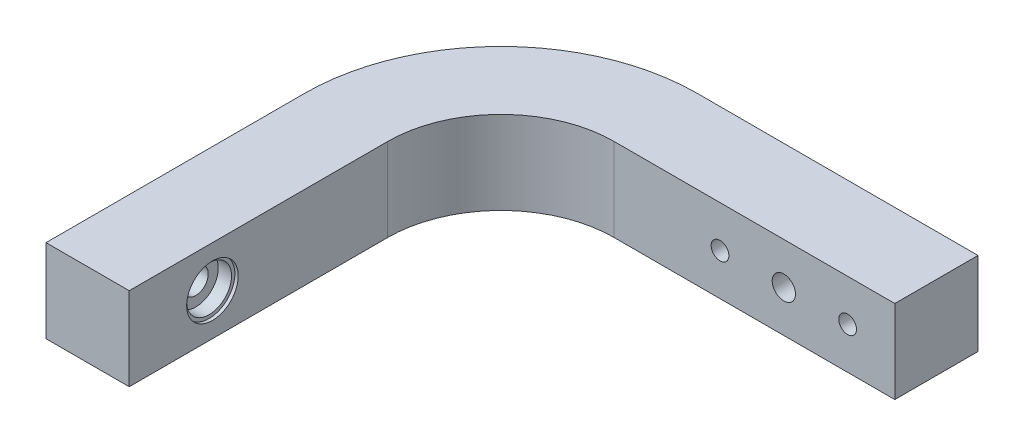
SolidWorks part; units mm, degrees
ref_plane "Front Plane" through (0, 0, 0) normal (0, 0, 1) x (1, 0, 0)
ref_plane "Top Plane" through (0, 0, 0) normal (0, 1, 0) x (1, 0, 0)
ref_plane "Right Plane" through (0, 0, 0) normal (1, 0, 0) x (0, 0, -1)
ref_axis "Z" through (0, 0, -59.2654) along (0, 0, 1)
sketch "Sketch1" plane through (0, 0, 0) normal (0, 1, 0) x (1, 0, 0)
  line L0 (-30.6, 0) -> (30.6, 0) construction
  line L1 (-66, -35.4) -> (-66, -82)
  line L2 (-66, -82) -> (-51, -82)
  line L3 (-51, -82) -> (-51, -35.4)
  line L4 (-30.6, -15) -> (30.6, -15) construction
  line L5 (0, -15) -> (0, 0) construction
  line L6 (51, -82) -> (51, -35.4) construction
  line L7 (66, -82) -> (51, -82) construction
  line L8 (66, -35.4) -> (66, -82) construction
  line L9 (30.6, 0) -> (30.6, -15) construction
  line L10 (20, -15) -> (20, 0)
  line L11 (-30.6, -15) -> (20, -15)
  line L12 (-30.6, 0) -> (20, 0)
  line L13 (0, 59.2654) -> (0, -30.9346) construction
  arc A0 (-30.6, 0) -> (-66, -35.4) centre (-30.6, -35.4) ccw
  arc A1 (-51, -35.4) -> (-30.6, -15) centre (-30.6, -35.4) cw
  arc A2 (51, -35.4) -> (30.6, -15) centre (30.6, -35.4) ccw construction
  arc A3 (30.6, 0) -> (66, -35.4) centre (30.6, -35.4) cw construction
  dimension "D3" = 20.4
  dimension "D1" = 102
  dimension "D2" = 15
  dimension "D4" = 67
  dimension "D5" = 20
extrude "Boss-Extrude1" add sketch "Sketch1" along normal blind 7.5 and the other way blind 7.5
sketch "Sketch2" plane through (-51, 0, 0) normal (-1, 0, 0) x (0, 0, 1)
  line L1 (45.1, 0) -> (-45.1, 0) construction
  line L2 (0, -8.25) -> (0, 8.25) construction
  circle A0 centre (67, 0) radius 2.25
  dimension "D1" = 4.5
  dimension "D2" = 67
extrude "Cut-Extrude1" cut sketch "Sketch2" against normal through all both and the other way through all
ref_axis "Axis2" through (-85.609, 0, 67) along (1, 0, 0)
sketch "Sketch3" plane through (0, 0, 0) normal (0, 0, -1) x (-1, 0, 0)
  line L0 (-11.5, 0) -> (11.5, 0) construction
  circle A0 centre (0, 0) radius 2.1
  circle A1 centre (-11.5, 0) radius 1.6
  circle A2 centre (11.5, 0) radius 1.6
  dimension "D1" = 4.2
  dimension "D3" = 3.2
  dimension "D2" = 23
extrude "Cut-Extrude2" cut sketch "Sketch3" against normal through all
sketch "Sketch5" plane through (0, 0, 0) normal (0, 1, 0) x (1, 0, 0)
  line L0 (-66, -71.65) -> (-65.4, -71.65)
  line L1 (-65.4, -71.65) -> (-65.4, -71.05)
  line L2 (-65.4, -71.05) -> (-63, -71.05)
  line L3 (-63, -71.05) -> (-63, -67)
  line L4 (-66, -71.65) -> (-66, -67)
  line L5 (-92.6767, -67) -> (-43.9581, -67) construction
  line L6 (-84.5878, -67) -> (-79.7197, -67) construction
  line L7 (-66, -67) -> (-63, -67)
  line L9 (-66, -35.4) -> (-66, -82) construction
  line L10 (-58.5, -78.0435) -> (-58.5, -69.815) construction
  line L11 (-66, -82) -> (-51, -82) construction
  line L12 (-51, -67) -> (-54, -67)
  line L13 (-51, -71.65) -> (-51, -67)
  line L14 (-54, -71.05) -> (-54, -67)
  line L15 (-51.6, -71.05) -> (-54, -71.05)
  line L16 (-51.6, -71.65) -> (-51.6, -71.05)
  line L17 (-51, -71.65) -> (-51.6, -71.65)
  point P14 (-58.5, -82)
  dimension "D1" = 0.6
  dimension "D2" = 4.65
  dimension "D3" = 8.1
  dimension "D4" = 3
revolve "bearing-seats" cut sketch "Sketch5" angle 360 about L6
equation "\"width\"= \"EyeDiameter\" + \"EyeClearance\""
equation "\"prongwidth\"= \"L2Thickness\""
equation "\"D2@Sketch1\"=\"prongwidth\""
equation "\"D3@Sketch1\"=\"width\"/5"
equation "\"pronglength\"= \"BasePlaneDistance\"'model implicitly adds clearance (of prongwidth) to the hole drilled at the baseplanedistance"
equation "\"D4@Sketch1\"=\"pronglength\""
equation "\"D1@Boss-Extrude1\"=\"prongwidth\"/2"
equation "\"D2@Boss-Extrude1\"=\"prongwidth\"/2"
equation "\"lbracket-plane-to-axis\"= \"BasePlaneDistance\""
equation "\"D2@Sketch2\"=\"lbracket-plane-to-axis\""
equation "\"EyeDiameter\" = 100"
equation "\"BasePlaneDistance\" = \"EyeDiameter\"/2+\"L2Thickness\"+\"EyeClearance\""
equation "\"EyeClearance\" = 2"
equation "\"D1@Sketch1\"=\"EyeDiameter\"+\"EyeClearance\""
equation "\"BearingDepth\"= 6"
equation "\"BearingHousingID\"=4.5"
equation "\"BearingFlangeThickness\"= 0.75"
equation "\"BearingFlangeOD\"=7.5"
equation "\"PrinterFilamentThickness\"= 0.1"
equation "\"ApplyPrinterOffset\"= 1'if 1, adjust hole sizes to try and make pressfits work with the 3d printer"
equation "\"L2Thickness\" = 15"
equation "\"L2_ID\" = 20"
equation "\"vx\" = 0"
equation "\"vy\" = 0"
equation "\"vz\" = 100"
equation "\"parametric_end\" = 1"
equation "\"Rw_3_xx\" = -(\"vz\")/sqr((\"vx\")^2 + (\"vz\")^2)"
equation "\"Rw_3_xy\" = 0"
equation "\"Rw_3_xz\" = (\"vx\")/sqr((\"vx\")^2 + (\"vz\")^2)"
equation "\"Rw_3_zx\" = (\"vx\")/sqr((\"vx\")^2 + (\"vy\")^2 + (\"vz\")^2)"
equation "\"Rw_3_zy\" = (\"vy\")/sqr((\"vx\")^2 + (\"vy\")^2 + (\"vz\")^2)"
equation "\"Rw_3_zz\" = (\"vz\")/sqr((\"vx\")^2 + (\"vy\")^2 + (\"vz\")^2)"
equation "\"Rw_3_yx\" = (\"vx\")*(\"vy\")/sqr((\"vx\")^4 + (\"vx\")^2*(\"vy\")^2 + 2*(\"vx\")^2*(\"vz\")^2 + (\"vy\")^2*(\"vz\")^2 + (\"vz\")^4)"
equation "\"Rw_3_yy\" = -sqr((\"vx\")^2 + (\"vz\")^2)/sqr((\"vx\")^2 + (\"vy\")^2 + (\"vz\")^2)"
equation "\"Rw_3_yz\" = (\"vy\")*(\"vz\")/sqr((\"vx\")^4 + (\"vx\")^2*(\"vy\")^2 + 2*(\"vx\")^2*(\"vz\")^2 + (\"vy\")^2*(\"vz\")^2 + (\"vz\")^4)"
equation "\"O2Targx\" = -\"BasePlaneDistance\"*(\"vx\")*(\"vy\")/sqr((\"vx\")^4 + (\"vx\")^2*(\"vy\")^2 + 2*(\"vx\")^2*(\"vz\")^2 + (\"vy\")^2*(\"vz\")^2 + (\"vz\")^4)"
equation "\"O2Targy\" = \"BasePlaneDistance\"*sqr((\"vx\")^2 + (\"vz\")^2)/sqr((\"vx\")^2 + (\"vy\")^2 + (\"vz\")^2)"
equation "\"O2Targz\" = -\"BasePlaneDistance\"*(\"vy\")*(\"vz\")/sqr((\"vx\")^4 + (\"vx\")^2*(\"vy\")^2 + 2*(\"vx\")^2*(\"vz\")^2 + (\"vy\")^2*(\"vz\")^2 + (\"vz\")^4)"
equation "\"O2Targx_0\" = -(\"BasePlaneDistance\")*sqr((\"vx\")^2 + (\"vz\")^2)/sqr((\"vx\")^2 + (\"vy\")^2 + (\"vz\")^2)"
equation "\"O2Targy_0\" = -(\"BasePlaneDistance\")*(\"vy\")*(\"vz\")/sqr((\"vx\")^4 + (\"vx\")^2*(\"vy\")^2 + 2*(\"vx\")^2*(\"vz\")^2 + (\"vy\")^2*(\"vz\")^2 + (\"vz\")^4)"
equation "\"O2Targz_0\" = (\"BasePlaneDistance\")*(\"vx\")*(\"vy\")/sqr((\"vx\")^4 + (\"vx\")^2*(\"vy\")^2 + 2*(\"vx\")^2*(\"vz\")^2 + (\"vy\")^2*(\"vz\")^2 + (\"vz\")^4) + (\"BasePlaneDistance\")"
equation "\"theta2_s1\" = arcsin(((\"BasePlaneDistance\") - (\"O2Targz_0\"))/(\"BasePlaneDistance\")) + pi"
equation "\"theta2_s2\" = -arcsin(((\"BasePlaneDistance\") - (\"O2Targz_0\"))/(\"BasePlaneDistance\"))"
equation "\"theta1_s1\" = arcsin((\"O2Targy_0\")/((\"BasePlaneDistance\")*cos((\"Theta2\")))) + pi"
equation "\"theta1_s2\" = -arcsin((\"O2Targy_0\")/((\"BasePlaneDistance\")*cos((\"Theta2\"))))"
equation "\"theta1_s3\" = -arccos(-(\"O2Targx_0\")/((\"BasePlaneDistance\")*cos((\"Theta2\")))) + 2*pi"
equation "\"theta1_s4\" = arccos(-(\"O2Targx_0\")/((\"BasePlaneDistance\")*cos((\"Theta2\"))))"
equation "\"Theta1\" = \"theta1_s2\" 'so far, theta1_s1 and theta1_s4 have agreed, and they agree with the sw constraint solver"
equation "\"Theta2\" = \"theta2_s2\""
equation "\"o2_x\" = -(\"BasePlaneDistance\")*cos((\"Theta1\"))*cos((\"Theta2\"))"
equation "\"o2_y\" = -(\"BasePlaneDistance\")*sin((\"Theta1\"))*cos((\"Theta2\"))"
equation "\"o2_z\" = (\"BasePlaneDistance\")*(sin((\"Theta2\")) + 1)"
equation "\"o1_x\" = (\"BasePlaneDistance\")*sin((\"Theta1\"))"
equation "\"o1_y\" = -(\"BasePlaneDistance\")*cos((\"Theta1\"))"
equation "\"o1_z\" = (\"BasePlaneDistance\")"
equation "\"Actuator1_Theta\" = atn(\"vx\"/\"vz\") 'ik solution for the single link joint"
equation "\"Actuator2_Theta\" = \"Theta1\"  'ik solution for the double link joint"
equation "\"MotorBaseThickness\" = 3 "
equation "\"BaseThickness\" = 3 "
equation "\"EncoderToMagnetAirgap\" = 1 'Encoder to magnet airgap"
equation "\"EncoderHeight\" = 1.192  'Height of the encoder"
equation "\"MagnetThickness\" = 0.5  'Magnet thickness"
equation "\"pcb_thickness\" = 1.6  'Thickness of the PCB"
equation "\"pcb_outer_diameter\" = 32 'the OD of the pcb"
equation "\"shaft_diameter\" = 4"
equation "\"D1@Sketch2\"=\"shaft_diameter\"*1.125"
equation "\"D2@Sketch5\"=\"ApplyPrinterOffset\" * \"PrinterFilamentThickness\" / 2 + 4.6"
equation "\"D3@Sketch5\"= \"ApplyPrinterOffset\" * \"PrinterFilamentThickness\"  + 8.00"
